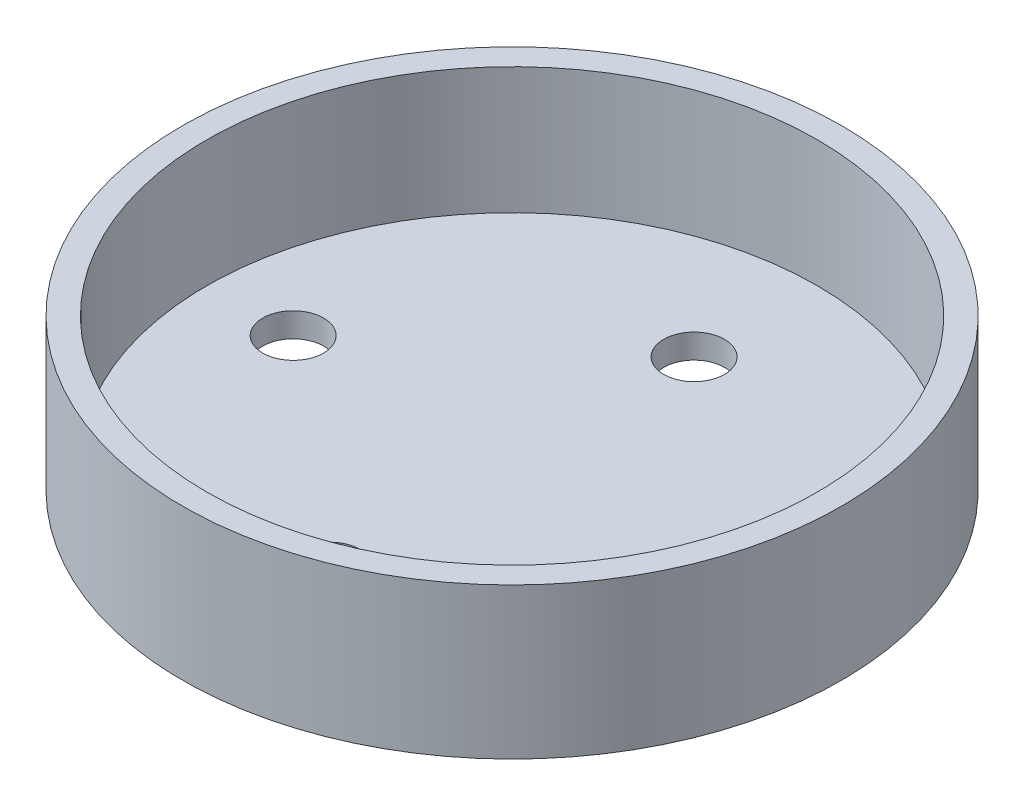
SolidWorks part; units mm, degrees
ref_plane "Front Plane" through (0, 0, 0) normal (0, 0, 1) x (1, 0, 0)
ref_plane "Top Plane" through (0, 0, 0) normal (0, 1, 0) x (1, 0, 0)
ref_plane "Right Plane" through (0, 0, 0) normal (1, 0, 0) x (0, 0, -1)
sketch "Sketch1" plane through (0, 0, 0) normal (0, 1, 0) x (1, 0, 0)
  circle A0 centre (0, 0) radius 13.55
  dimension "D1" = 27.1
extrude "Boss-Extrude1" add sketch "Sketch1" along normal blind 6.2
shell "Shell1" thickness 1 removed face at (0, 6.2, 13.55)
hole_wizard "M3x0.5 Tapped Hole1" positions "Sketch2" profile "Sketch3" tap size "M3x0.5" standard "ANSI Metric"
sketch "Sketch2" plane through (0, 0, 0) normal (0, -1, 0) x (-1, 0, 0)
  line L0 (0, 0) -> (0, -13.55) construction
  line L2 (0, 0) -> (13.55, 0) construction
  line L3 (0, -7.4831) -> (-9, 0) construction
  line L5 (9, 0) -> (0, 7.4831) construction
  circle A0 centre (0, 0) radius 13.55 construction
  point P0 (9, 0)
  point P2 (0, -7.4831)
  point P20 (-9, 0)
  point P22 (0, 7.4831)
  dimension "D1" = 18
  dimension "D2" = 14.9662
sketch "Sketch3" plane through (-9, 0, 0) normal (1, 0, 0) x (0, 0, -1)
  line L0 (0, 0) -> (0, 8.2511)
  line L1 (0, 8.2511) -> (1.25, 7.5)
  line L2 (1.25, 7.5) -> (1.25, 0)
  line L5 (1.25, 0) -> (0, 0)
  line L10 (0, 8.2511) -> (-1.25, 7.5) construction
  line L11 (0, -6.35) -> (0, 107.95) construction
  dimension "Tap Drill Dia." = 2.5
  dimension "Tap Drill Depth" = 7.5
  dimension "Drill Angle" = 118
cosmetic thread "Hole Thread1" parameters "D1"=6, "D2"=3
cosmetic thread "Hole Thread2" parameters "D1"=6, "D2"=3
cosmetic thread "Hole Thread3" parameters "D1"=6, "D2"=3
cosmetic thread "Hole Thread4" parameters "D1"=6, "D2"=3
